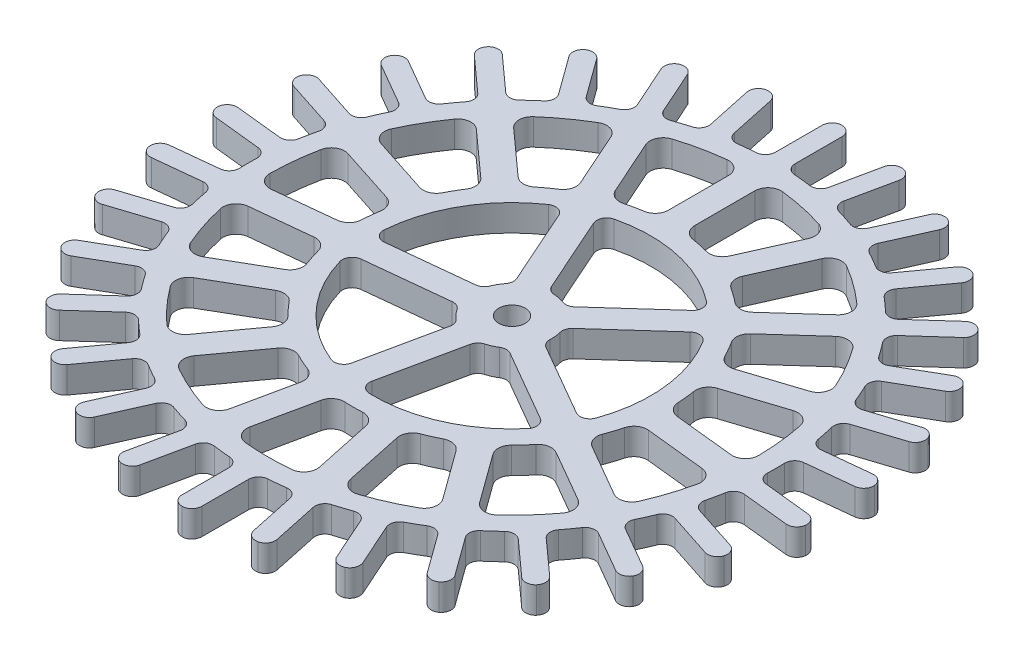
SolidWorks part; units mm, degrees
ref_plane "Front Plane" through (0, 0, 0) normal (0, 0, 1) x (1, 0, 0)
ref_plane "Top Plane" through (0, 0, 0) normal (0, 1, 0) x (1, 0, 0)
ref_plane "Right Plane" through (0, 0, 0) normal (1, 0, 0) x (0, 0, -1)
sketch "Sketch1" plane through (0, 0, 0) normal (0, 1, 0) x (1, 0, 0)
  circle A0 centre (0, 0) radius 127
  dimension "D1" = 254
extrude "Boss-Extrude1" add sketch "Sketch1" along normal blind 12.7
sketch "Sketch2" plane through (0, 12.7, 0) normal (0, 1, 0) x (1, 0, 0)
  line L0 (0, 158.6607) -> (0, 0) construction
  line L1 (-4.7625, 126.9107) -> (4.7625, 126.9107)
  line L2 (-4.7625, 158.6607) -> (4.7625, 158.6607)
  line L3 (4.7625, 158.6607) -> (4.7625, 126.9107)
  line L4 (-4.7625, 158.6607) -> (-4.7625, 126.9107)
  line L8 (-4.7625, 126.9107) -> (4.7625, 126.9107)
  circle A0 centre (0, 0) radius 127 construction
  circle M4 centre (0, 0) radius 127
  dimension "D1" = 31.75
  dimension "D2" = 9.525
extrude "Boss-Extrude2" add sketch "Sketch2" against normal up to surface (12.7 mm away) contours L2 L0 L3 M4 | L0 L2 L4 M4 up to face at (0, 0, 127)
fillet "Fillet1" radius 4.7625 4 edges at (-4.7625, 6.35, -158.6607) (-4.7625, 6.35, -126.9107) (4.7625, 6.35, -126.9107) (4.7625, 6.35, -158.6607)
pattern_circular "CirPattern1" count 30 over 360 about axis through (0, 0, 0) along (0, 1, 0) of "Boss-Extrude2", "Fillet1"
sketch "Sketch3" plane through (0, 12.7, 0) normal (0, 1, 0) x (1, 0, 0)
  circle A0 centre (0, 0) radius 6.35
  dimension "D1" = 12.7
extrude "Cut-Extrude1" cut sketch "Sketch3" against normal through all
sketch "Sketch4" plane through (0, 12.7, 0) normal (0, 1, 0) x (1, 0, 0)
  line L0 (41.9105, 109.7446) -> (25.0845, 71.9528)
  line L1 (6.35, 117.3033) -> (6.35, 75.935)
  line L2 (0, 0) -> (0, 201.1843) construction
  line L3 (0, 0) -> (83.784, 188.182) construction
  arc A0 (6.35, 75.935) -> (25.0845, 71.9528) centre (0, 0) cw
  arc A1 (6.35, 117.3033) -> (41.9105, 109.7446) centre (0, 0) cw
  circle A3 centre (0, 0) radius 127 construction
  dimension "D1" = 24
  dimension "D4" = 9.525
  dimension "D5" = 76.2
  dimension "D2" = 12.7
  dimension "D3" = 12.7
extrude "Cut-Extrude2" cut sketch "Sketch4" against normal through all contours A1 L0 A0 L1
fillet "Fillet2" radius 6.35 4 edges at (6.35, 6.35, -75.935) (25.0845, 6.35, -71.9528) (41.9105, 6.35, -109.7446) (6.35, 6.35, -117.3033)
pattern_circular "CirPattern3" count 15 over 360 about axis through (0, 0, 0) along (0, 1, 0) of "Fillet2", "Cut-Extrude2"
sketch "Sketch6" plane through (0, 12.7, 0) normal (0, 1, 0) x (1, 0, 0)
  line L0 (-21.1949, 63.2166) -> (-1.5042, 18.9905)
  line L1 (45.075, 49.1305) -> (9.0983, 16.7369)
  line L2 (0, 0) -> (79.6649, 71.7306) construction
  line L3 (86.2899, 69.151) -> (64.8652, 49.8602) construction
  line L4 (0, 0) -> (-48.1643, 108.1788) construction
  line L5 (-39.1015, 103.4354) -> (-27.3754, 77.0981) construction
  line L6 (77.7919, 78.5889) -> (56.3673, 59.2981) construction
  arc A0 (-21.1949, 63.2166) -> (45.075, 49.1305) centre (0, 0) cw
  arc A1 (-1.5042, 18.9905) -> (9.0983, 16.7369) centre (0, 0) cw
  arc A2 (19.9148, 73.5516) -> (11.7231, 75.2928) centre (0, 0) ccw construction
  dimension "D1" = 19.05
  dimension "D2" = 9.525
extrude "Cut-Extrude3" cut sketch "Sketch6" against normal through all
fillet "Fillet3" radius 4.7625 4 edges at (45.075, 6.35, -49.1305) (9.0983, 6.35, -16.7369) (-1.5042, 6.35, -18.9905) (-21.1949, 6.35, -63.2166)
pattern_circular "CirPattern5" count 5 over 360 about axis through (0, 0, 0) along (0, 1, 0) of "Fillet3", "Cut-Extrude3"
sketch "Sketch5" plane through (0, 12.7, 0) normal (0, 1, 0) x (1, 0, 0)
  arc A0 (-25.4435, 64.1023) -> (37.6936, 57.7553) centre (0, 0) cw
